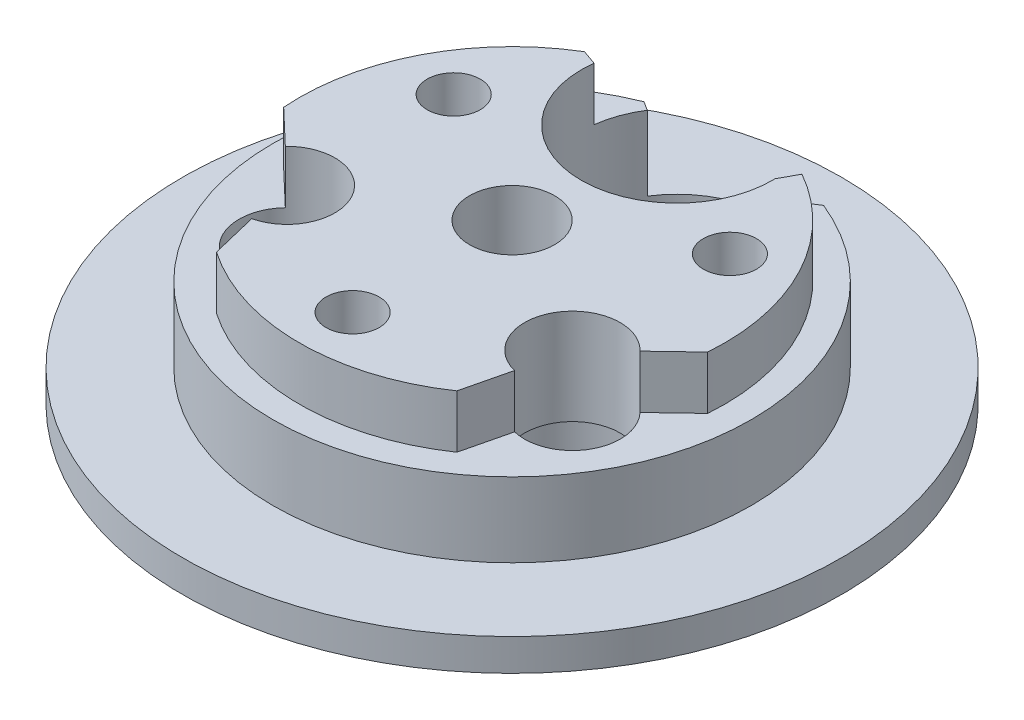
SolidWorks part; units mm, degrees
ref_plane "Front Plane" through (0, 0, 0) normal (0, 0, 1) x (1, 0, 0)
ref_plane "Top Plane" through (0, 0, 0) normal (0, 1, 0) x (1, 0, 0)
ref_plane "Right Plane" through (0, 0, 0) normal (1, 0, 0) x (0, 0, -1)
sketch "Sketch1" plane through (0, 0, 0) normal (0, 1, 0) x (1, 0, 0)
  line L0 (-8.4455, 20.8548) -> (0, 15.5)
  line L1 (0, 15.5) -> (8.4455, 20.8548)
  arc A0 (-8.4455, 20.8548) -> (8.4455, 20.8548) centre (0, 0) ccw
  arc A1 (-7.6009, 20.3194) -> (7.6009, 20.3194) centre (0, 15.5) ccw
  circle A2 centre (13.4234, -7.75) radius 9
  circle A3 centre (-13.4234, -7.75) radius 9
  arc A4 (-8.4455, 20.8548) -> (8.4455, 20.8548) centre (0, 15.5) ccw
  dimension "D1" = 45
  dimension "D3" = 18
  dimension "D5" = 20
  dimension "D2" = 15.5
  dimension "D4" = 3
extrude "Boss-Extrude1" add sketch "Sketch1" along normal blind 7 contours A3 A0 A2 A1 | L0 A4 L1 A1 region at (0, 0, 0.6011) region at (-8.1582, 0, -20.3741)
sketch "Sketch2" plane through (0, 7, 0) normal (0, 1, 0) x (1, 0, 0)
  line L6 (-19.9404, -1.5429) -> (-13.4234, -7.75)
  line L7 (-13.4234, -7.75) -> (-11.3064, -16.4975)
  line L8 (11.3064, -16.4975) -> (13.4234, -7.75)
  line L9 (13.4234, -7.75) -> (19.9404, -1.5429)
  line L12 (8.4455, 20.8548) -> (7.6009, 20.3194)
  line L14 (-7.6009, 20.3194) -> (-8.4455, 20.8548)
  arc A1 (-12.3649, -12.1237) -> (-16.6819, -4.6464) centre (-13.4234, -7.75) ccw
  arc A5 (16.6819, -4.6464) -> (12.3649, -12.1237) centre (13.4234, -7.75) ccw
  arc A6 (-15.2232, -16.5682) -> (-21.9601, -4.8995) centre (-13.4234, -7.75) ccw
  arc A7 (-15.2232, -16.5682) -> (15.2232, -16.5682) centre (0, 0) ccw
  arc A8 (21.9601, -4.8995) -> (15.2232, -16.5682) centre (13.4234, -7.75) ccw
  arc A9 (21.9601, -4.8995) -> (8.4455, 20.8548) centre (0, 0) ccw
  arc A10 (-7.6009, 20.3194) -> (7.6009, 20.3194) centre (0, 15.5) ccw
  arc A11 (-8.4455, 20.8548) -> (-21.9601, -4.8995) centre (0, 0) ccw
  arc A12 (-11.3064, -16.4975) -> (-19.9404, -1.5429) centre (-13.4234, -7.75) ccw
  arc A14 (19.9404, -1.5429) -> (11.3064, -16.4975) centre (13.4234, -7.75) ccw
  arc A19 (-8.634, 18.0403) -> (-19.9404, -1.5429) centre (0, 0) ccw
  arc A24 (19.9404, -1.5429) -> (8.634, 18.0403) centre (0, 0) ccw
  arc A25 (3.3685, 18.4839) -> (0, 20) centre (0, 15.5) ccw [skipped]
  arc A27 (-11.3064, -16.4975) -> (11.3064, -16.4975) centre (0, 0) ccw
  arc A28 (-12.012, -13.5816) -> (-17.7681, -3.6119) centre (-13.4234, -7.75) ccw
  arc A32 (17.7681, -3.6119) -> (12.012, -13.5816) centre (13.4234, -7.75) ccw
  arc A39 (-8.634, 18.0403) -> (8.634, 18.0403) centre (0, 15.5) ccw
  arc M11 (15.2232, -16.5682) -> (21.9601, -4.8995) centre (13.4234, -7.75) cw
  dimension "D3" = 9
  dimension "D1" = 0
  dimension "D4" = 3
extrude "Boss-Extrude3" add sketch "Sketch2" along normal blind 5 and the other way blind 7 contours A14 A39 A12 | A39 | A14 | A5 | A12 | A1 | A32 L9 L8 M11 region at (-5.8333, 7, 3.3679) region at (0, 7, 0) region at (-8.3633, 7, 4.8286) region at (5.8333, 7, 3.3679) region at (8.3633, 7, 4.8286)
sketch "Sketch3" plane through (0, 0, 0) normal (0, -1, 0) x (1, 0, 0)
  line L4 (19.9404, 1.5429) -> (16.6819, 4.6464)
  line L5 (19.9404, 1.5429) -> (16.6819, 4.6464)
  line L6 (12.3649, 12.1237) -> (11.3064, 16.4975)
  line L7 (12.3649, 12.1237) -> (11.3064, 16.4975)
  line L12 (-11.3064, 16.4975) -> (-12.3649, 12.1237)
  line L13 (-11.3064, 16.4975) -> (-12.3649, 12.1237)
  line L14 (-16.6819, 4.6464) -> (-19.9404, 1.5429)
  line L15 (-16.6819, 4.6464) -> (-19.9404, 1.5429)
  line L18 (-8.4455, -20.8548) -> (-7.6009, -20.3194)
  line L19 (-8.4455, -20.8548) -> (-7.6009, -20.3194)
  line L20 (7.6009, -20.3194) -> (8.4455, -20.8548)
  line L21 (7.6009, -20.3194) -> (8.4455, -20.8548)
  circle A0 centre (0, -15.5) radius 9
  arc A1 (-21.9601, 4.8995) -> (-15.2232, 16.5682) centre (-13.4234, 7.75) ccw
  arc A2 (15.2232, 16.5682) -> (21.9601, 4.8995) centre (13.4234, 7.75) ccw
  circle A3 centre (-13.4234, 7.75) radius 4.5
  circle A4 centre (13.4234, 7.75) radius 4.5
  circle A5 centre (0, 0) radius 22.5
  arc A10 (19.9404, 1.5429) -> (21.9601, 4.8995) centre (13.4234, 7.75) ccw
  arc A11 (12.3649, 12.1237) -> (16.6819, 4.6464) centre (13.4234, 7.75) ccw
  arc A12 (15.2232, 16.5682) -> (11.3064, 16.4975) centre (13.4234, 7.75) ccw
  arc A13 (15.2232, 16.5682) -> (-15.2232, 16.5682) centre (0, 0) ccw
  arc A14 (-11.3064, 16.4975) -> (-15.2232, 16.5682) centre (-13.4234, 7.75) ccw
  arc A15 (12.3649, 12.1237) -> (16.6819, 4.6464) centre (13.4234, 7.75) ccw
  arc A16 (-21.9601, 4.8995) -> (-19.9404, 1.5429) centre (-13.4234, 7.75) ccw
  arc A17 (-21.9601, 4.8995) -> (-8.4455, -20.8548) centre (0, 0) ccw
  arc A18 (-16.6819, 4.6464) -> (-12.3649, 12.1237) centre (-13.4234, 7.75) ccw
  arc A19 (8.4455, -20.8548) -> (21.9601, 4.8995) centre (0, 0) ccw
  arc A20 (19.9404, 1.5429) -> (21.9601, 4.8995) centre (13.4234, 7.75) ccw
  arc A22 (15.2232, 16.5682) -> (11.3064, 16.4975) centre (13.4234, 7.75) ccw
  arc A23 (15.2232, 16.5682) -> (-15.2232, 16.5682) centre (0, 0) ccw
  arc A24 (-11.3064, 16.4975) -> (-15.2232, 16.5682) centre (-13.4234, 7.75) ccw
  arc A26 (-21.9601, 4.8995) -> (-19.9404, 1.5429) centre (-13.4234, 7.75) ccw
  arc A27 (-21.9601, 4.8995) -> (-8.4455, -20.8548) centre (0, 0) ccw
  arc A29 (8.4455, -20.8548) -> (21.9601, 4.8995) centre (0, 0) ccw
  arc A36 (-16.6819, 4.6464) -> (-12.3649, 12.1237) centre (-13.4234, 7.75) ccw
  arc A37 (7.6009, -20.3194) -> (-7.6009, -20.3194) centre (0, -15.5) ccw
  arc A38 (7.6009, -20.3194) -> (-7.6009, -20.3194) centre (0, -15.5) ccw
  arc M17 (21.9601, 4.8995) -> (19.9404, 1.5429) centre (13.4234, 7.75) cw
  line M18 (19.9404, 1.5429) -> (16.6819, 4.6464)
  arc M19 (16.6819, 4.6464) -> (12.3649, 12.1237) centre (13.4234, 7.75) cw
  line M20 (12.3649, 12.1237) -> (11.3064, 16.4975)
  arc M21 (11.3064, 16.4975) -> (15.2232, 16.5682) centre (13.4234, 7.75) cw
  arc M23 (-15.2232, 16.5682) -> (-11.3064, 16.4975) centre (-13.4234, 7.75) cw
  line M24 (-11.3064, 16.4975) -> (-12.3649, 12.1237)
  arc M25 (-12.3649, 12.1237) -> (-16.6819, 4.6464) centre (-13.4234, 7.75) cw
  line M26 (-16.6819, 4.6464) -> (-19.9404, 1.5429)
  arc M27 (-19.9404, 1.5429) -> (-21.9601, 4.8995) centre (-13.4234, 7.75) cw
  dimension "D1" = 0
  dimension "D2" = 3
extrude "Boss-Extrude5" add sketch "Sketch3" against normal blind 7 contours A5 A3 M23 M27 M26 M24 | A1 M26 M24 M25 | A5 A4 M17 M21 M20 M18 | A2 M20 M18 M19 region at (5.8333, 0, 3.3679) region at (18.4392, 0, 3.2291) region at (-13.2642, 0, 16.5629) region at (-5.8333, 0, 3.3679)
sketch "Sketch5" plane through (0, 12, 0) normal (0, 1, 0) x (1, 0, 0)
  line L0 (0, 0) -> (0, -22.5) construction
  line L1 (0, 0) -> (-19.4856, 11.25) construction
  line L2 (0, 0) -> (19.4856, 11.25) construction
  circle A0 centre (0, 0) radius 4
  arc A1 (-8.4455, 20.8548) -> (8.4455, 20.8548) centre (0, 0) ccw construction
  circle A5 centre (-12.9904, 7.5) radius 2.5
  circle A6 centre (12.9904, 7.5) radius 2.5
  circle A7 centre (0, -15) radius 2.5
  dimension "D1" = 8
  dimension "D3" = 15
  dimension "D5" = 5
  dimension "D2" = 3
  dimension "D4" = 3
extrude "Cut-Extrude2" cut sketch "Sketch5" against normal through all
sketch "Sketch6" plane through (0, 0, 0) normal (0, -1, 0) x (1, 0, 0)
  circle A0 centre (13.4234, 7.75) radius 4.5 construction
  circle A1 centre (-13.4234, 7.75) radius 4.5 construction
  circle A2 centre (13.4234, 7.75) radius 4.5
  circle A3 centre (-13.4234, 7.75) radius 4.5
  circle A4 centre (-13.4234, 7.75) radius 6
  circle A5 centre (13.4234, 7.75) radius 6
  dimension "D1" = 12
  dimension "D2" = 12
extrude "Cut-Extrude3" cut sketch "Sketch6" against normal blind 3
sketch "Sketch7" plane through (0, 0, 0) normal (0, -1, 0) x (1, 0, 0)
  line L2 (7.6009, -20.3194) -> (8.4455, -20.8548)
  line L3 (-8.4455, -20.8548) -> (-7.6009, -20.3194)
  line L4 (7.6009, -20.3194) -> (8.4455, -20.8548)
  line L5 (-8.4455, -20.8548) -> (-7.6009, -20.3194)
  circle A0 centre (0, 0) radius 31
  circle A1 centre (0, 0) radius 4 construction
  arc A2 (8.4455, -20.8548) -> (-8.4455, -20.8548) centre (0, 0) ccw
  arc A3 (7.6009, -20.3194) -> (-7.6009, -20.3194) centre (0, -15.5) ccw
  arc A4 (8.4455, -20.8548) -> (-8.4455, -20.8548) centre (0, 0) ccw
  arc A5 (7.6009, -20.3194) -> (-7.6009, -20.3194) centre (0, -15.5) ccw
  circle A6 centre (12.9904, -7.5) radius 2.5 construction
  circle A7 centre (-12.9904, -7.5) radius 2.5 construction
  circle A8 centre (13.4234, 7.75) radius 4.5 construction
  circle A9 centre (13.4234, 7.75) radius 6 construction
  circle A10 centre (-13.4234, 7.75) radius 6 construction
  circle A11 centre (-13.4234, 7.75) radius 4.5 construction
  circle A12 centre (0, 15) radius 2.5 construction
  circle A13 centre (0, 0) radius 4
  circle A14 centre (12.9904, -7.5) radius 2.5
  circle A15 centre (-12.9904, -7.5) radius 2.5
  circle A16 centre (13.4234, 7.75) radius 4.5
  circle A17 centre (13.4234, 7.75) radius 6
  circle A18 centre (-13.4234, 7.75) radius 6
  circle A19 centre (-13.4234, 7.75) radius 4.5
  circle A20 centre (0, 15) radius 2.5
  circle A21 centre (0, -15.5) radius 9
  circle M6 centre (-13.4234, 7.75) radius 6
  circle M7 centre (13.4234, 7.75) radius 6
  circle M8 centre (0, 15) radius 2.5
  circle M9 centre (12.9904, -7.5) radius 2.5
  circle M10 centre (-12.9904, -7.5) radius 2.5
  circle M11 centre (0, 0) radius 4
  line M12 (7.6009, -20.3194) -> (8.4455, -20.8548)
  arc M13 (8.4455, -20.8548) -> (-8.4455, -20.8548) centre (0, 0) ccw
  line M14 (-8.4455, -20.8548) -> (-7.6009, -20.3194)
  arc M15 (-7.6009, -20.3194) -> (7.6009, -20.3194) centre (0, -15.5) cw
  dimension "D2" = 62
  dimension "D1" = 0
extrude "Boss-Extrude6" add sketch "Sketch7" along normal blind 3 contours A0 A21 M14 M13 M12 | M15 M12 M13 M14 M7 M9 M11 M10 M8 M6 region at (9.2432, 0, -18.1834) region at (-30.1232, 0, 0)
chamfer "Chamfer1" distance 2 angle 45 2 edges at (-8.634, 9.5, -18.0403) (8.634, 9.5, -18.0403) first distance on face at (-15.8039, 9.5, -9.1244) first distance on face at (0, 6.5, -18.2689)
